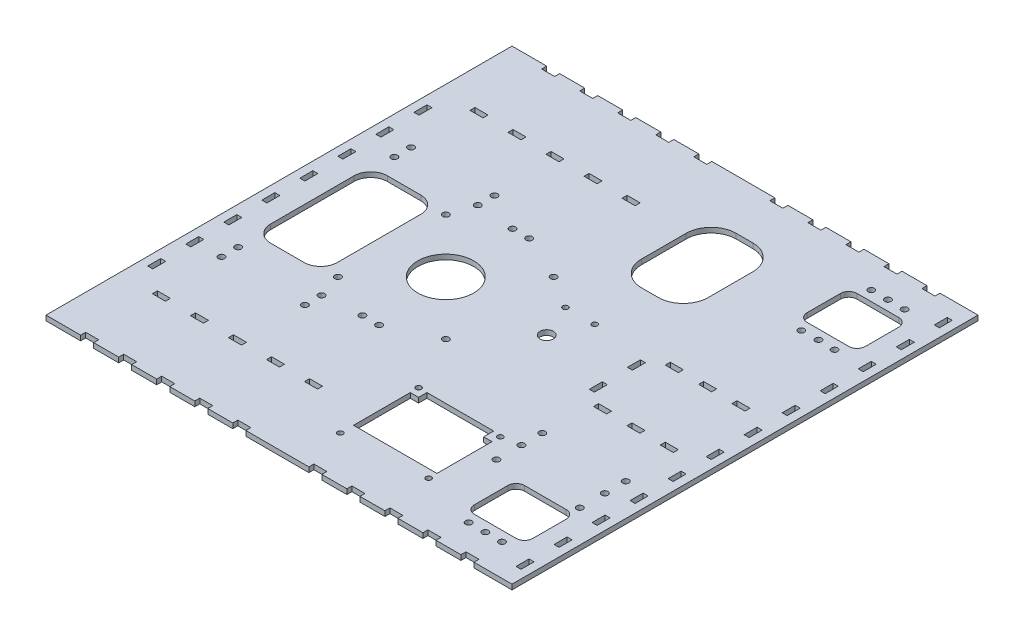
SolidWorks part; units mm, degrees
material "ENPH 253 Hardboard"
ref_plane "Front Plane" through (0, 0, 0) normal (0, 0, 1) x (1, 0, 0)
ref_plane "Top Plane" through (0, 0, 0) normal (0, 1, 0) x (1, 0, 0)
ref_plane "Right Plane" through (0, 0, 0) normal (1, 0, 0) x (0, 0, -1)
sketch "Sketch1" plane through (0, 0, 0) normal (0, 1, 0) x (1, 0, 0)
  line L0 (0, -139.7) -> (0, 139.7) construction
  line L1 (-139.7, 139.7) -> (139.7, 139.7)
  line L2 (-139.7, 139.7) -> (-139.7, -139.7)
  line L3 (-139.7, -139.7) -> (139.7, -139.7)
  line L4 (139.7, 139.7) -> (139.7, -139.7)
  line L5 (-139.7, 139.7) -> (139.7, -139.7) construction
  line L6 (-139.7, -139.7) -> (139.7, 139.7) construction
  line L12 (-139.7, 0) -> (139.7, 0) construction
  point P0 (0, 0)
  dimension "D1" = 279.4
  dimension "D2" = 279.4
extrude "Boss-Extrude1" add sketch "Sketch1" along normal blind 3
sketch "Sketch3" plane through (0, 0, 0) normal (0, -1, 0) x (-1, 0, 0)
  line L0 (-139.7, -139.7) -> (-139.7, 139.7) construction
  line L1 (-134.7, 129.3) -> (-131.7, 129.3)
  line L2 (-134.7, 129.3) -> (-134.7, 121.5)
  line L3 (-134.7, 121.5) -> (-131.7, 121.5)
  line L4 (-131.7, 129.3) -> (-131.7, 121.5)
  line L5 (-139.7, 139.7) -> (139.7, 139.7) construction
  dimension "D1" = 5
  dimension "D2" = 10.4
  dimension "D3" = 7.8
  dimension "D4" = 3
extrude "Cut-Extrude2" cut sketch "Sketch3" against normal through all
pattern_linear "LPattern1" count 12 spacing 22.8 along (0, 0, 1) of "Cut-Extrude2"
sketch "Sketch5" plane through (0, 0, 0) normal (0, -1, 0) x (1, 0, 0)
  line L0 (139.7, -139.7) -> (-139.7, -139.7) construction
  line L1 (109.1, -139.7) -> (116.9, -139.7)
  line L2 (109.1, -139.7) -> (109.1, -136.7)
  line L3 (109.1, -136.7) -> (116.9, -136.7)
  line L4 (116.9, -139.7) -> (116.9, -136.7)
  line L5 (139.7, 139.7) -> (139.7, -139.7) construction
  dimension "D1" = 22.8
  dimension "D2" = 7.8
  dimension "D3" = 3
extrude "Cut-Extrude3" cut sketch "Sketch5" against normal through all
pattern_linear "LPattern2" count 11 spacing 22.8 along (-1, 0, 0) skipping (5, 0) of "Cut-Extrude3"
mirror "Mirror2" about plane through (0, 0, 0) normal (0, 0, 1) of "LPattern2"
sketch "Sketch6" plane through (0, 0, 0) normal (0, -1, 0) x (1, 0, 0)
  line L0 (63.5, -139.7) -> (48.5, -139.7) construction
  line L1 (-134.7, -83.7) -> (-131.7, -83.7)
  line L2 (-134.7, -83.7) -> (-134.7, -75.9)
  line L3 (-134.7, -75.9) -> (-131.7, -75.9)
  line L4 (-131.7, -83.7) -> (-131.7, -75.9)
  line L5 (-139.7, -139.7) -> (-139.7, 139.7) construction
  dimension "D1" = 56
  dimension "D2" = 5
  dimension "D3" = 3
  dimension "D4" = 7.8
extrude "Cut-Extrude4" cut sketch "Sketch6" against normal through all
pattern_linear "LPattern3" count 8 spacing 22.8 along (0, 0, 1) of "Cut-Extrude4"
sketch "Sketch7" plane through (0, 0, 0) normal (0, -1, 0) x (-1, 0, 0)
  line L1 (139.7, 139.7) -> (139.7, -139.7) construction
  line L3 (-63.5, 139.7) -> (-48.5, 139.7) construction
  circle A0 centre (39.7, 0) radius 16.75
  dimension "D1" = 33.5
  dimension "D2" = 100
  dimension "D3" = 139.7
extrude "Cut-Extrude5" cut sketch "Sketch7" against normal through all
hole_wizard "#6 Clearance Hole1" positions "Sketch8" profile "Sketch9" hole size "#6" standard "ANSI Inch" end condition through all
sketch "Sketch8" plane through (0, 3, 0) normal (0, 1, 0) x (1, 0, 0)
  line L0 (-72.025, -32.325) -> (-72.025, 32.325) construction
  line L1 (-72.025, 32.325) -> (-7.375, 32.325) construction
  line L2 (-7.375, 32.325) -> (-7.375, -32.325) construction
  line L3 (-7.375, -32.325) -> (-72.025, -32.325) construction
  point P0 (-72.025, -32.325)
  point P2 (-72.025, 32.325)
  point P4 (-7.375, 32.325)
  point P6 (-7.375, -32.325)
  dimension "D1" = 64.65
  dimension "D2" = 64.65
  dimension "D3" = 90
  dimension "D4" = 64.65
  dimension "D5" = 32.325
  dimension "D6" = 32.325
sketch "Sketch9" plane through (-72.025, 3, 32.325) normal (1, 0, 0) x (0, 0, 1)
  line L0 (0, 0) -> (0, 3)
  line L1 (0, 3) -> (1.8986, 3)
  line L2 (1.8986, 3) -> (1.8986, 0)
  line L5 (1.8986, 0) -> (0, 0)
  line L11 (0, -6.35) -> (0, 107.95) construction
  dimension "Thru Hole Dia." = 3.7973
  dimension "Thru Hole Depth" = 3
hole_wizard "#6 Clearance Hole2" positions "Sketch10" profile "Sketch11" hole size "#6" standard "ANSI Inch" end condition through all
sketch "Sketch10" plane through (0, 3, 0) normal (0, 1, 0) x (1, 0, 0)
  line L1 (-118.9, 139.7) -> (-139.7, 139.7) construction
  line L2 (-139.7, -139.7) -> (-118.9, -139.7) construction
  line L3 (-73.3, 139.7) -> (-88.3, 139.7) construction
  line L4 (-88.3, -139.7) -> (-73.3, -139.7) construction
  line L5 (-139.7, 139.7) -> (-139.7, -139.7) construction
  point P0 (-117.36, 56.83)
  point P2 (-67.36, 56.83)
  point P4 (-117.36, -56.83)
  point P6 (-67.36, -56.83)
  point P22 (-67.36, -46.83)
  point P24 (-117.36, -46.83)
  point P26 (-67.36, 46.83)
  point P28 (-117.36, 46.83)
  dimension "D2" = 50
  dimension "D3" = 22.34
  dimension "D4" = 50
  dimension "D5" = 82.87
  dimension "D6" = 82.87
  dimension "D7" = 82.87
  dimension "D8" = 82.87
  dimension "D9" = 10
  dimension "D10" = 10
  dimension "D11" = 50
  dimension "D12" = 10
  dimension "D13" = 10
  dimension "D14" = 50
  dimension "D15" = 22.34
  dimension "D16" = 22.34
  dimension "D17" = 22.34
sketch "Sketch11" plane through (-117.36, 3, -56.83) normal (1, 0, 0) x (0, 0, 1)
  line L0 (0, 0) -> (0, 3)
  line L1 (0, 3) -> (1.8986, 3)
  line L2 (1.8986, 3) -> (1.8986, 0)
  line L5 (1.8986, 0) -> (0, 0)
  line L11 (0, -6.35) -> (0, 107.95) construction
  dimension "Thru Hole Dia." = 3.7973
  dimension "Thru Hole Depth" = 3
sketch "Sketch14" plane through (0, 0, 0) normal (0, -1, 0) x (-1, 0, 0)
  line L0 (139.7, 139.7) -> (139.7, -139.7) construction
  line L1 (-17.9, 139.7) -> (19.9, 139.7) construction
  circle A0 centre (-20.8, 0) radius 4
  point P6 (-12.05, 20)
  point P7 (-29.55, 20)
  dimension "D1" = 8
  dimension "D2" = 160.5
  dimension "D3" = 139.7
  dimension "D4" = 8.75
  dimension "D5" = 20
  dimension "D6" = 8.75
extrude "Cut-Extrude6" cut sketch "Sketch14" against normal through all
sketch "Sketch16" plane through (0, 0, 0) normal (0, -1, 0) x (1, 0, 0)
  line L0 (-139.7, -139.7) -> (-139.7, 139.7) construction
  line L1 (-118.9, 96.7) -> (-111.1, 96.7)
  line L2 (-118.9, 96.7) -> (-118.9, 93.7)
  line L3 (-118.9, 93.7) -> (-111.1, 93.7)
  line L4 (-111.1, 96.7) -> (-111.1, 93.7)
  line L7 (-111.1, 136.7) -> (-118.9, 136.7) construction
  dimension "D1" = 20.8
  dimension "D2" = 7.8
  dimension "D3" = 40
  dimension "D4" = 3
extrude "Cut-Extrude8" cut sketch "Sketch16" against normal through all
pattern_linear "LPattern5" count 5 spacing 22.8 along (1, 0, 0) of "Cut-Extrude8"
mirror "Mirror4" about plane through (0, 0, 0) normal (0, 0, 1) of "LPattern5"
sketch "Sketch17" plane through (0, 0, 0) normal (0, -1, 0) x (1, 0, 0)
  line L1 (119.7, 23) -> (111.9, 23)
  line L2 (119.7, 23) -> (119.7, 20)
  line L3 (119.7, 20) -> (111.9, 20)
  line L4 (111.9, 23) -> (111.9, 20)
  line L5 (94.1, 139.7) -> (109.1, 139.7) construction
  line L6 (139.7, 139.7) -> (139.7, -139.7) construction
  point P8 (119.7, 21.5)
  dimension "D1" = 116.7
  dimension "D2" = 20
  dimension "D3" = 7.8
  dimension "D4" = 3
extrude "Cut-Extrude9" cut sketch "Sketch17" against normal through all
pattern_linear "LPattern6" count 3 spacing 20 along (-1, 0, 0) of "Cut-Extrude9"
sketch "Sketch18" plane through (0, 0, 0) normal (0, -1, 0) x (-1, 0, 0)
  line L0 (-139.7, -139.7) -> (-139.7, 139.7) construction
  line L1 (-64.7, -15.3) -> (-61.7, -15.3)
  line L2 (-64.7, -15.3) -> (-64.7, -7.5)
  line L3 (-64.7, -7.5) -> (-61.7, -7.5)
  line L4 (-61.7, -15.3) -> (-61.7, -7.5)
  line L5 (-71.3, -139.7) -> (-86.3, -139.7) construction
  dimension "D1" = 7.8
  dimension "D2" = 3
  dimension "D3" = 75
  dimension "D4" = 124.4
extrude "Cut-Extrude10" cut sketch "Sketch18" against normal through all
mirror "Mirror5" about plane through (0, 0, 0) normal (0, 0, 1) of "Cut-Extrude10", "LPattern6", "Cut-Extrude9"
sketch "Sketch19" plane through (0, 0, 0) normal (0, -1, 0) x (1, 0, 0)
  line L0 (0, 0) -> (139.7, 0) construction
  line L1 (24.7, -109.7) -> (34.7, -109.7)
  line L2 (9.7, -94.7) -> (9.7, -68)
  line L3 (24.7, -53) -> (34.7, -53)
  line L4 (49.7, -94.7) -> (49.7, -68)
  line L9 (139.7, 139.7) -> (139.7, -139.7) construction
  line L10 (86.3, -139.7) -> (71.3, -139.7) construction
  line L11 (79.7, -23) -> (71.9, -23) construction
  line L16 (-139.7, -139.7) -> (-139.7, 139.7) construction
  line L17 (-89.7, 35) -> (-109.7, 35)
  line L18 (-79.7, 25) -> (-79.7, -25)
  line L19 (-89.7, -35) -> (-109.7, -35)
  line L20 (-119.7, 25) -> (-119.7, -25)
  line L21 (9.7, 104.7) -> (59.7, 104.7)
  line L22 (9.7, 65.7) -> (59.7, 65.7) construction
  line L23 (9.7, 65.7) -> (9.7, 109.7) construction
  line L24 (9.7, 109.7) -> (59.7, 109.7) construction
  line L25 (59.7, 65.7) -> (59.7, 109.7) construction
  line L29 (14.7, 65.7) -> (54.7, 65.7)
  line L30 (25.7, 139.7) -> (40.7, 139.7) construction
  line L32 (59.7, 104.7) -> (59.7, 71.7) construction
  line L34 (9.7, 104.7) -> (9.7, 70.7) construction
  line L35 (139.7, 139.7) -> (139.7, -139.7) construction
  line L38 (9.7, 104.7) -> (9.7, 70.7)
  line L39 (9.7, 70.7) -> (14.7, 70.7)
  line L40 (14.7, 70.7) -> (14.7, 65.7)
  line L41 (54.7, 65.7) -> (54.7, 71.7)
  line L42 (54.7, 71.7) -> (59.7, 71.7)
  line L43 (59.7, 71.7) -> (59.7, 104.7)
  arc A1 (34.7, -53) -> (49.7, -68) centre (34.7, -68) cw
  arc A2 (34.7, -109.7) -> (49.7, -94.7) centre (34.7, -94.7) ccw
  arc A3 (24.7, -109.7) -> (9.7, -94.7) centre (24.7, -94.7) cw
  arc A4 (9.7, -68) -> (24.7, -53) centre (24.7, -68) cw
  circle A9 centre (-39.7, 0) radius 16.75 construction
  arc A10 (-79.7, -25) -> (-89.7, -35) centre (-89.7, -25) cw
  arc A11 (-89.7, 35) -> (-79.7, 25) centre (-89.7, 25) cw
  arc A12 (-109.7, 35) -> (-119.7, 25) centre (-109.7, 25) ccw
  arc A13 (-109.7, -35) -> (-119.7, -25) centre (-109.7, -25) cw
  point P43 (-79.7, -35)
  point P46 (-79.7, 35)
  dimension "D9" = 35
  dimension "D10" = 10
  dimension "D11" = 44
  dimension "D12" = 50
  dimension "D1" = 15
  dimension "D2" = 30
  dimension "D3" = 90
  dimension "D4" = 30
  dimension "D5" = 40
  dimension "D6" = 70
  dimension "D7" = 20
  dimension "D8" = 40
  dimension "D13" = 5
  dimension "D15" = 5
  dimension "D17" = 30
  dimension "D18" = 80
  dimension "D14" = 6
extrude "Cut-Extrude11" cut sketch "Sketch19" against normal through all
hole_wizard "#4 Clearance Hole1" positions "Sketch20" profile "Sketch21" hole size "#4" standard "ANSI Inch" end condition through all
sketch "Sketch20" plane through (0, 3, 0) normal (0, 1, 0) x (1, 0, 0)
  line L0 (9.7, -104.7) -> (9.7, -70.7) construction
  line L1 (59.7, -71.7) -> (59.7, -104.7) construction
  point P0 (9.7, -65.7)
  point P2 (59.7, -66.7)
  point P4 (59.7, -109.7)
  point P6 (9.7, -112.7)
  dimension "D1" = 5
  dimension "D2" = 8
  dimension "D3" = 5
  dimension "D4" = 1
sketch "Sketch21" plane through (9.7, 3, 65.7) normal (1, 0, 0) x (0, 0, 1)
  line L0 (0, 0) -> (0, 3)
  line L1 (0, 3) -> (1.6319, 3)
  line L2 (1.6319, 3) -> (1.6319, 0)
  line L5 (1.6319, 0) -> (0, 0)
  line L11 (0, -6.35) -> (0, 107.95) construction
  dimension "Thru Hole Dia." = 3.2639
  dimension "Thru Hole Depth" = 3
sketch "Sketch22" plane through (0, 3, 0) normal (0, 1, 0) x (1, 0, 0)
  line L5 (92.2, -84.7) -> (117.2, -84.7)
  line L6 (87.2, -89.7) -> (87.2, -109.7)
  line L7 (92.2, -114.7) -> (117.2, -114.7)
  line L8 (122.2, -89.7) -> (122.2, -109.7)
  line L9 (139.7, -139.7) -> (139.7, 139.7) construction
  line L10 (94.1, -139.7) -> (109.1, -139.7) construction
  line L11 (139.7, 0) -> (94.1968, 0) construction
  line L12 (92.2, 114.7) -> (117.2, 114.7)
  line L13 (122.2, 89.7) -> (122.2, 109.7)
  line L14 (92.2, 84.7) -> (117.2, 84.7)
  line L15 (87.2, 89.7) -> (87.2, 109.7)
  arc A0 (87.2, -109.7) -> (92.2, -114.7) centre (92.2, -109.7) ccw
  arc A1 (92.2, -84.7) -> (87.2, -89.7) centre (92.2, -89.7) ccw
  arc A2 (117.2, -84.7) -> (122.2, -89.7) centre (117.2, -89.7) cw
  arc A3 (117.2, -114.7) -> (122.2, -109.7) centre (117.2, -109.7) ccw
  arc A4 (92.2, 84.7) -> (87.2, 89.7) centre (92.2, 89.7) cw
  arc A5 (122.2, 89.7) -> (117.2, 84.7) centre (117.2, 89.7) cw
  arc A6 (117.2, 114.7) -> (122.2, 109.7) centre (117.2, 109.7) cw
  arc A7 (92.2, 114.7) -> (87.2, 109.7) centre (92.2, 109.7) ccw
  point P2 (87.2, -114.7)
  point P9 (87.2, -84.7)
  point P23 (122.2, -84.7)
  point P26 (122.2, -114.7)
  point P29 (87.2, 84.7)
  point P32 (122.2, 84.7)
  point P35 (122.2, 114.7)
  point P38 (87.2, 114.7)
  dimension "D1" = 5
  dimension "D5" = 17.5
  dimension "D6" = 35
  dimension "D7" = 25
  dimension "D8" = 30
extrude "Cut-Extrude12" cut sketch "Sketch22" against normal up to next contours L8 L5 L6 L7 | L15 L14 L13 L12 region at (104.7, 3, 99.7) region at (104.7, 3, -99.7)
hole_wizard "#6 Clearance Hole3" positions "Sketch25" profile "Sketch26" hole size "#6" standard "ANSI Inch" end condition through all
sketch "Sketch25" plane through (0, 3, 0) normal (0, 1, 0) x (1, 0, 0)
  line L0 (70.35, -52.2) -> (70.35, -79.7) construction
  line L2 (70.35, -79.7) -> (120.35, -79.7) construction
  line L3 (120.35, -79.7) -> (120.35, -52.2) construction
  line L4 (120.35, -52.2) -> (70.35, -52.2) construction
  line L6 (70.35, -64.7) -> (120.35, -64.7) construction
  line L8 (92.2, -84.7) -> (117.2, -84.7) construction
  line L9 (104.7, 79.0309) -> (104.7, 120.7) construction
  line L10 (104.7, 120.7) -> (94.7, 120.7) construction
  line L11 (94.7, 120.7) -> (94.7, 78.7) construction
  line L12 (94.7, 78.7) -> (114.7, 78.7) construction
  line L13 (114.7, 78.7) -> (114.7, 120.7) construction
  line L14 (114.7, 120.7) -> (94.7, 120.7) construction
  line L16 (92.2, 84.7) -> (117.2, 84.7) construction
  line L17 (92.2, 114.7) -> (117.2, 114.7) construction
  line L18 (0, 0) -> (139.7, 0) construction
  line L19 (139.7, -139.7) -> (139.7, 139.7) construction
  point P0 (94.7, 120.7)
  point P2 (114.7, 120.7)
  point P4 (114.7, 78.7)
  point P6 (94.7, 78.7)
  point P8 (104.7, 79.0309)
  point P10 (104.7, 120.7)
  point P12 (70.35, -52.2)
  point P14 (70.35, -79.7)
  point P16 (70.35, -64.7)
  point P18 (120.35, -64.7)
  point P20 (120.35, -52.2)
  point P22 (120.35, -79.7)
  point P43 (104.7, -84.7)
  point P56 (104.7, 84.7)
  point P59 (161.7487, 56.9763)
  point P68 (114.7, -120.7)
  point P69 (104.7, -120.7)
  point P70 (94.7, -120.7)
  point P71 (-44.7, 45)
  point P73 (-34.7, 45)
  point P75 (-44.7, -45)
  point P77 (-34.7, -45)
  dimension "D1" = 27.5
  dimension "D2" = 5
  dimension "D3" = 15
  dimension "D4" = 50
  dimension "D5" = 15.65
  dimension "D6" = 20
  dimension "D7" = 10
  dimension "D8" = 6
  dimension "D9" = 6
  dimension "D10" = 90
  dimension "D11" = 45
  dimension "D12" = 10
  dimension "D13" = 34.7
sketch "Sketch26" plane through (94.7, 3, -120.7) normal (1, 0, 0) x (0, 0, 1)
  line L0 (0, 0) -> (0, 3)
  line L1 (0, 3) -> (1.8986, 3)
  line L2 (1.8986, 3) -> (1.8986, 0)
  line L5 (1.8986, 0) -> (0, 0)
  line L11 (0, -6.35) -> (0, 107.95) construction
  dimension "Thru Hole Dia." = 3.7973
  dimension "Thru Hole Depth" = 3
hole_wizard "#4 Clearance Hole2" positions "Sketch27" profile "Sketch28" hole size "#4" standard "ANSI Inch" end condition up to next
sketch "Sketch27" plane through (0, 3, 0) normal (0, 1, 0) x (1, 0, 0)
  point P0 (12.05, 20)
  point P2 (29.55, 20)
sketch "Sketch28" plane through (12.05, 3, -20) normal (1, 0, 0) x (0, 0, 1)
  line L0 (0, 0) -> (0, 3)
  line L1 (0, 3) -> (1.6319, 3)
  line L2 (1.6319, 3) -> (1.6319, 0)
  line L5 (1.6319, 0) -> (0, 0)
  line L11 (0, -6.35) -> (0, 107.95) construction
  dimension "Thru Hole Dia." = 3.2639
  dimension "Thru Hole Depth" = 3
equation "\"45mmm\"=50"
equation "\"D11@Sketch25\"=\"D10@Sketch25\"/2"
